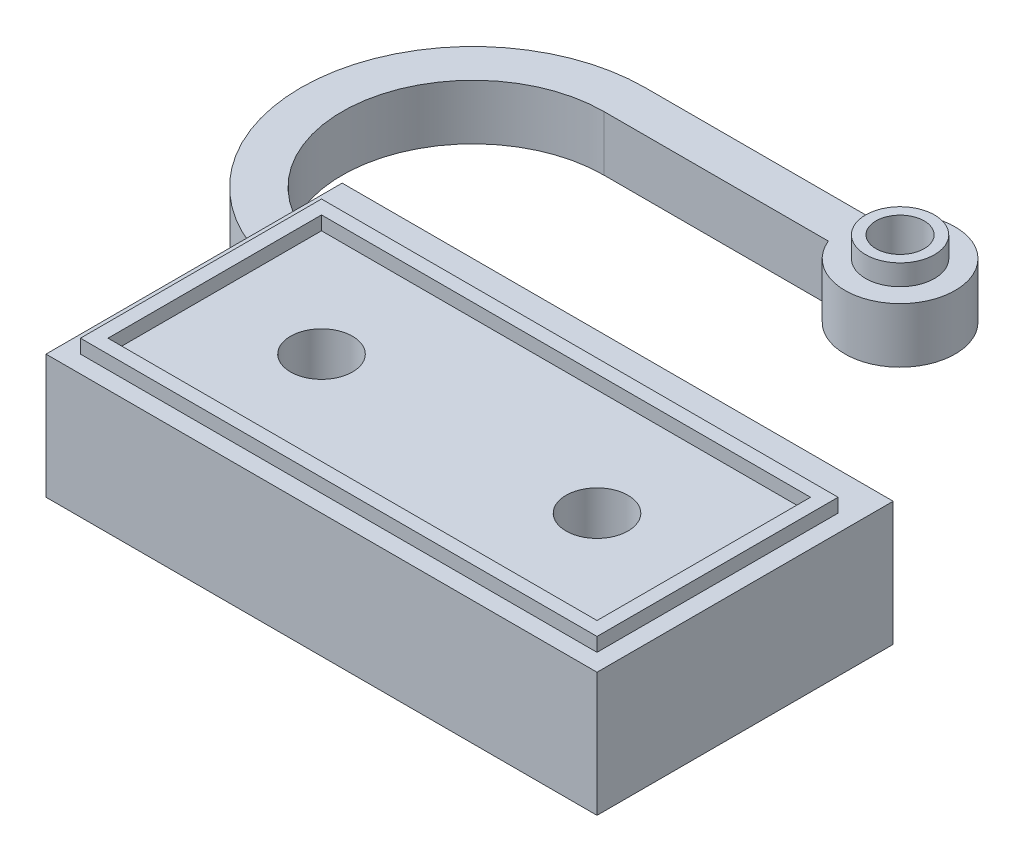
SolidWorks part; units mm, degrees
ref_plane "Front Plane" through (0, 0, 0) normal (0, 0, 1) x (1, 0, 0)
ref_plane "Top Plane" through (0, 0, 0) normal (0, 1, 0) x (1, 0, 0)
ref_plane "Right Plane" through (0, 0, 0) normal (1, 0, 0) x (0, 0, -1)
sketch "Sketch1" plane through (0, 0, 0) normal (0, 1, 0) x (1, 0, 0)
  line L0 (20, 8.5) -> (20, 11.5)
  line L1 (-20, 10) -> (20, 10)
  line L2 (-20, 10) -> (-20, -10)
  line L3 (-20, -10) -> (20, -10)
  line L4 (20, 10) -> (20, -10)
  line L5 (0, -10) -> (0, 10) construction
  line L6 (-20, 0) -> (20, 0) construction
  line L7 (-20, 11.5) -> (20, 11.5) construction
  line L8 (-20, 11.5) -> (-20, 8.5) construction
  line L9 (-20, 8.5) -> (20, 8.5) construction
  line L10 (20, 11.5) -> (20, 8.5) construction
  line L11 (0, 8.5) -> (0, 11.5) construction
  line L12 (-20, 10) -> (20, 10) construction
  line L13 (20, 11.5) -> (-20, 11.5)
  line L14 (-20, 8.5) -> (20, 8.5)
  line L15 (-20, 30.5) -> (-3.7081, 30.5)
  line L16 (-20, 33.5) -> (0, 33.5) construction
  line L17 (-20, 33.5) -> (-20, 30.5) construction
  line L18 (-20, 30.5) -> (0, 30.5) construction
  line L19 (0, 33.5) -> (0, 30.5) construction
  line L20 (-10, 30.5) -> (-10, 33.5) construction
  line L21 (-20, 32) -> (0, 32) construction
  line L22 (-3.7081, 33.5) -> (-20, 33.5)
  line L24 (-20, 11.5) -> (20, 11.5)
  line L25 (-20, 11.5) -> (-20, 8.5)
  line L26 (-20, 8.5) -> (20, 8.5)
  line L27 (20, 11.5) -> (20, 8.5)
  line L28 (0, 8.5) -> (0, 11.5) construction
  line L29 (-20, 10) -> (20, 10) construction
  circle A0 centre (-10, 0) radius 2.25
  circle A1 centre (10, 0) radius 2.25
  arc A2 (-20, 10) -> (-20, 32) centre (-20, 21) cw construction
  arc A3 (-20, 33.5) -> (-20, 8.5) centre (-20, 21) ccw construction
  arc A4 (-20, 30.5) -> (-20, 11.5) centre (-20, 21) ccw construction
  arc A5 (-20, 30.5) -> (-20, 33.5) centre (-20, 32) ccw construction
  arc A6 (-20, 8.5) -> (-20, 11.5) centre (-20, 10) ccw construction
  arc A7 (-20, 11.5) -> (-20, 30.5) centre (-20, 21) cw
  arc A9 (-20, 33.5) -> (-20, 8.5) centre (-20, 21) ccw
  circle A10 centre (0, 32) radius 1.75
  circle A11 centre (0, 32) radius 4 construction
  arc A12 (-3.7081, 30.5) -> (-3.7081, 33.5) centre (0, 32) ccw
  point P0 (0, 0)
  point P10 (-31, 21)
  point P460 (-10, 32)
  dimension "D4" = 4.5
  dimension "D5" = 1.5
  dimension "D7" = 8
  dimension "D8" = 3.5
  dimension "D1" = 20
  dimension "D2" = 40
  dimension "D3" = 10
  dimension "D6" = 11
extrude "Boss-Extrude3" add sketch "Sketch1" along normal blind 9 contours L14 L2 L3 L4 A0 A1 | L13 L25 L1 L0 | L2 L14 L0 L1 region at (0, 0, -9.25) region at (0, 0, 0.7837) region at (0, 0, -10.75)
extrude "Boss-Extrude4" add sketch "Sketch1<5>" along normal blind 4 contours L15 A12 L22 A9 L2 L25 A7 A10 region at (-32.043, 0, -21)
sketch "Sketch1<5>" plane through (0, 0, 0) normal (0, 1, 0) x (1, 0, 0) same geometry as "Sketch1"
sketch "Sketch2" plane through (0, 4, 0) normal (0, 1, 0) x (1, 0, 0)
  circle A0 centre (0, 32) radius 1.75
  circle A1 centre (0, 32) radius 2.5
  dimension "D1" = 5
  dimension "D2" = 3.5
extrude "Boss-Extrude5" add sketch "Sketch2" along normal blind 1.5
sketch "Sketch3" plane through (0, 9, 0) normal (0, 1, 0) x (1, 0, 0)
  line L0 (-18.75, 8.75) -> (18.75, 8.75)
  line L1 (-17.75, 7.75) -> (17.75, 7.75)
  line L2 (-17.75, 7.75) -> (-17.75, -7.75)
  line L3 (-17.75, -7.75) -> (17.75, -7.75)
  line L4 (17.75, 7.75) -> (17.75, -7.75)
  line L5 (0, -7.75) -> (0, 7.75) construction
  line L6 (-17.75, 0) -> (17.75, 0) construction
  line L7 (18.75, 8.75) -> (18.75, -8.75)
  line L8 (-18.75, -8.75) -> (18.75, -8.75)
  line L9 (-18.75, 8.75) -> (-18.75, -8.75)
  point P0 (0, 0)
  dimension "D1" = 15.5
  dimension "D2" = 35.5
  dimension "D3" = 1
extrude "Boss-Extrude6" add sketch "Sketch3" along normal blind 1 contours L0 L7 L8 L9 | L2 L1 L4 L3
